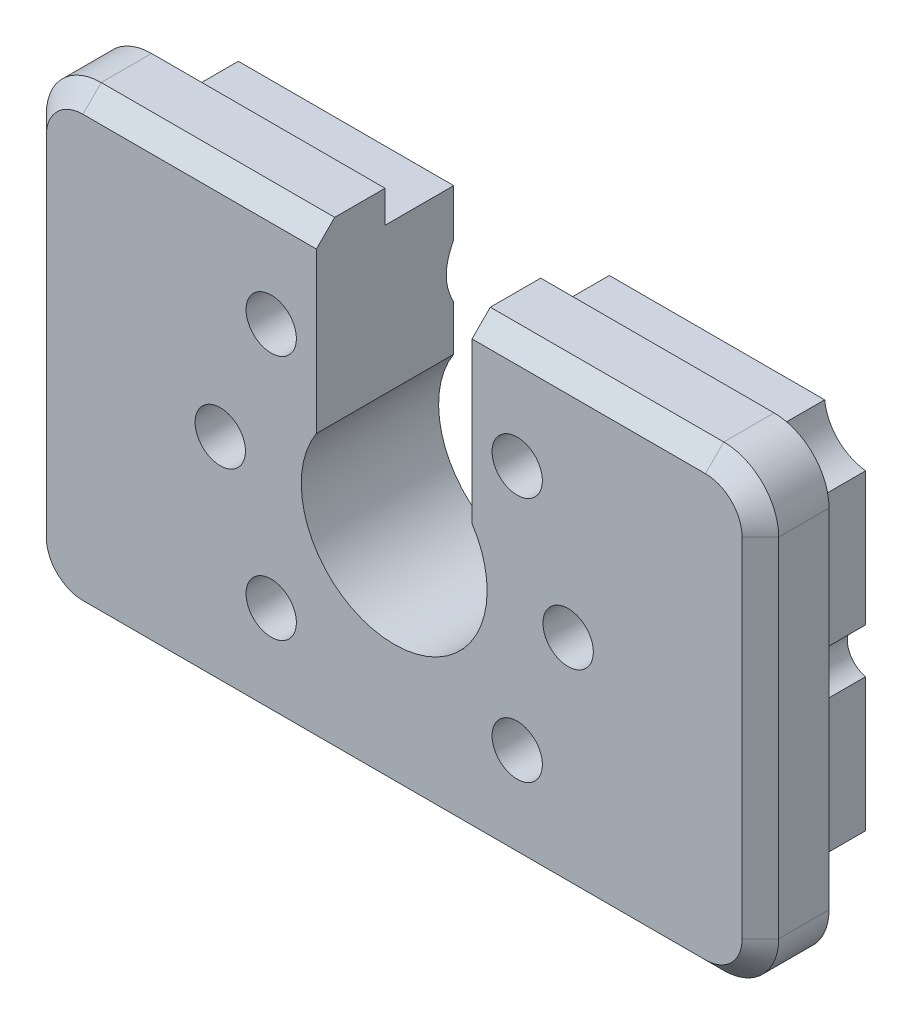
SolidWorks part; units mm, degrees
material "PET"
ref_plane "Front Plane" through (0, 0, 0) normal (0, 0, 1) x (1, 0, 0)
ref_plane "Top Plane" through (0, 0, 0) normal (0, 1, 0) x (1, 0, 0)
ref_plane "Right Plane" through (0, 0, 0) normal (1, 0, 0) x (0, 0, -1)
sketch "Sketch1" plane through (0, 0, 0) normal (0, 0, 1) x (1, 0, 0)
  line L1 (40, -25) -> (-40, -25)
  line L2 (40, -25) -> (40, 25)
  line L3 (40, 25) -> (-40, 25)
  line L4 (-40, -25) -> (-40, 25)
  line L5 (40, -25) -> (-40, 25) construction
  line L6 (40, 25) -> (-40, -25) construction
  point P0 (0, 0)
  dimension "D1" = 50
  dimension "D2" = 80
extrude "Boss-Extrude1" add sketch "Sketch1" against normal blind 7.5
sketch "Sketch2" plane through (0, 0, -7.5) normal (0, 0, -1) x (-1, 0, 0)
  line L8 (36.5, -21.5) -> (36.5, 21.5)
  line L9 (36.5, 21.5) -> (-36.5, 21.5)
  line L10 (-36.5, 21.5) -> (-36.5, -21.5)
  line L11 (-36.5, -21.5) -> (36.5, -21.5)
  line L12 (36.5, -21.5) -> (36.5, 21.5)
  line L13 (36.5, 21.5) -> (-36.5, 21.5)
  line L14 (-36.5, 21.5) -> (-36.5, -21.5)
  line L15 (-36.5, -21.5) -> (36.5, -21.5)
  dimension "D1" = 3.5
extrude "Boss-Extrude2" add sketch "Sketch2" along normal blind 7.5
sketch "Sketch3" plane through (0, 0, 0) normal (0, 0, 1) x (1, 0, 0)
  line L0 (0, 0) -> (0, 51.1675) construction
  line L1 (40, 25) -> (-40, 25) construction
  line L2 (8.5, 5.5473) -> (-8.5, 5.5473) construction
  line L3 (8.5, 5.5473) -> (8.5, 25)
  line L4 (8.5, 25) -> (-8.5, 25)
  line L5 (-8.5, 5.5473) -> (-8.5, 25)
  line L6 (8.5, 5.5473) -> (-8.5, 25) construction
  line L7 (8.5, 25) -> (-8.5, 5.5473) construction
  line L8 (0, 0) -> (-19, 0) construction
  arc A0 (-8.5, 5.5473) -> (8.5, 5.5473) centre (0, 0) ccw
  circle A1 centre (-19, 0) radius 2.75
  circle A2 centre (-13.435, 13.435) radius 2.75
  circle A3 centre (0, 19) radius 2.75 construction
  circle A4 centre (13.435, 13.435) radius 2.75
  circle A5 centre (19, 0) radius 2.75
  circle A6 centre (13.435, -13.435) radius 2.75
  circle A7 centre (0, -19) radius 2.75 construction
  circle A8 centre (-13.435, -13.435) radius 2.75
  point P3 (0, 15.2736)
  point P28 (0, 0)
  dimension "D1" = 20.3
  dimension "D4" = 5.5
  dimension "D2" = 17
  dimension "D3" = 19
  dimension "D5" = 8
extrude "Cut-Extrude1" cut sketch "Sketch3" against normal through all
fillet "Fillet1" radius 6 4 edges at (40, -25, -3.75) (-40, -25, -3.75) (-40, 25, -3.75) (40, 25, -3.75)
sketch "Sketch4" plane through (0, 0, -15) normal (0, 0, -1) x (-1, 0, 0)
  line L0 (-37, 22) -> (-37, -22) construction
  line L1 (-40, -19) -> (-40, 19) construction
  line L2 (-34, 25) -> (-8.5, 25) construction
  line L4 (34, -25) -> (-34, -25) construction
  line L5 (-37, -22) -> (0, -22) construction
  line L6 (0, 0) -> (0, -22) construction
  circle A0 centre (-37, 22) radius 5
  circle A1 centre (-37, -22) radius 5
  circle A2 centre (-37, 0) radius 2.5
  circle A3 centre (0, -22) radius 2.5
  circle A4 centre (37, -22) radius 5
  circle A5 centre (37, 0) radius 2.5
  circle A6 centre (37, 22) radius 5
  dimension "D4" = 5
  dimension "D5" = 10
  dimension "D1" = 3
  dimension "D2" = 3
  dimension "D3" = 3
extrude "Cut-Extrude2" cut sketch "Sketch4" against normal up to surface (7.5 mm away) up to face at (0, 5.8125, -7.5)
chamfer "Chamfer1" distance 2 angle 45 9 edges at (-21.25, 25, 0) (-38.2426, 23.2426, 0) (-40, 0, 0) (-38.2426, -23.2426, 0) (0, -25, 0) (38.2426, -23.2426, 0) (40, 0, 0) (38.2426, 23.2426, 0) (21.25, 25, 0)
chamfer "Chamfer2" distance 3 angle 45 6 edges at (16.185, -13.435, -15) (-16.25, 0, -15) (-10.685, -13.435, -15) (21.75, 0, -15) (16.185, 13.435, -15) (-10.685, 13.435, -15)
equation "\"hole_radius\" = 10.15mm"
equation "\"D1@Sketch3\"=\"hole_radius\"*2"
